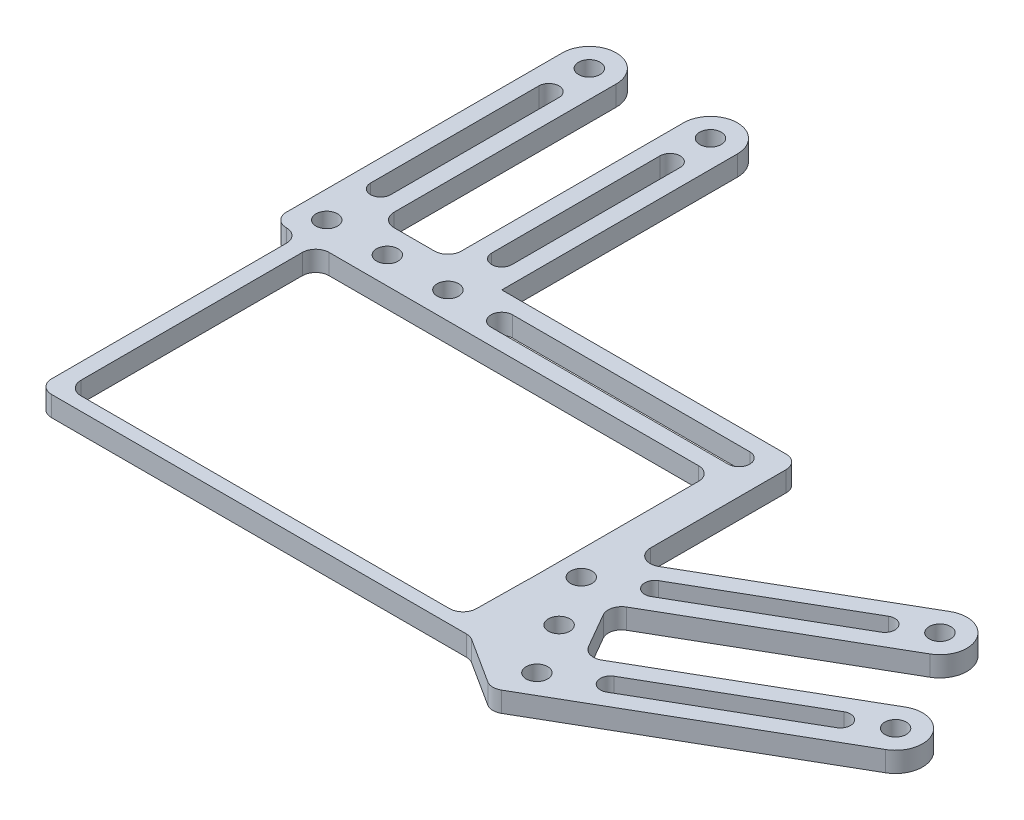
SolidWorks part; units mm, degrees
material "Thornel Mat VMA"
ref_plane "Front Plane" through (0, 0, 0) normal (0, 0, 1) x (1, 0, 0)
ref_plane "Top Plane" through (0, 0, 0) normal (0, 1, 0) x (1, 0, 0)
ref_plane "Right Plane" through (0, 0, 0) normal (1, 0, 0) x (0, 0, -1)
other "Configuration Table"
sketch "Sketch1" plane through (0, 0, 0) normal (0, 1, 0) x (1, 0, 0)
  line L0 (0, -4) -> (0, -42.8799)
  line L1 (0, -42.8799) -> (64.2212, -42.8799)
  line B0 (-4, -4) -> (61.235, -4)
  line B1 (61.235, -4) -> (61.235, -28.7731)
  line B2 (61.235, -28.7731) -> (72.3984, -48.1086)
  line B3 (72.3984, -48.1086) -> (79.3266, -44.1086)
  line B4 (64.8625, -27.0561) -> (73.8625, -42.6445) construction
  line B5 (79.3266, -44.1086) -> (66.235, -21.4334)
  line B6 (66.235, -21.4334) -> (66.235, 4)
  line B7 (66.235, 4) -> (-4, 4)
  line B8 (-4, 4) -> (-4, -4)
  line B9 (2.3607, -4) -> (2.3607, -40.8799)
  line B10 (2.3607, -40.8799) -> (61.0934, -40.8799)
  line B11 (61.0934, -40.8799) -> (72.3984, -48.1086)
  line B12 (61.235, -28.7731) -> (61.0934, -40.8799)
  line B13 (0, 0) -> (-4, 0) construction
  line B14 (73.8625, -42.6445) -> (75.8625, -46.1086) construction
  circle B15 centre (73.8625, -42.6445) radius 1.6
  circle B16 centre (69.3625, -34.8503) radius 1.6
  circle B17 centre (64.8625, -27.0561) radius 1.6
  circle B18 centre (0, 0) radius 1.6
  circle B19 centre (9, 0) radius 1.6
  circle B20 centre (18, 0) radius 1.6
  dimension "D1" = 2
sketch_block_instance "Block1-1"
sketch_block "Block1"
extrude "Boss-Extrude1" add sketch "Sketch1" along normal blind 3 contours B7 B8 B0 B1 B2 B3 B5 B6 B20 B19 B18 B17 B16 B15 | B11 B10 B9 B0 L0 L1 | B2 B12 B11 region at (1.1804, 0, 4.7507) region at (-2, 0, 3.0172) region at (64.909, 0, 39.2539)
fillet "Fillet1" radius 2 5 edges at (61.235, 1.5, 28.7731) (61.235, 1.5, 4) (2.3607, 1.5, 40.8799) (61.0934, 1.5, 40.8799) (2.3607, 1.5, 4)
fillet "Fillet2" radius 2 9 edges at (0, 1.5, 4) (-4, 1.5, 4) (-4, 1.5, -4) (66.235, 1.5, -4) (66.235, 1.5, 21.4334) (79.3266, 1.5, 44.1086) (72.3984, 1.5, 48.1086) (64.2212, 1.5, 42.8799) (0, 1.5, 42.8799)
sketch "Sketch2" plane through (0, 3, 0) normal (0, 1, 0) x (1, 0, 0)
  line L0 (26, 0) -> (61.235, 0) construction
  line L1 (26, 1.6) -> (61.235, 1.6)
  line L2 (26, -1.6) -> (61.235, -1.6)
  line L3 (61.235, -6) -> (61.235, -28.7614) construction
  arc A0 (26, 1.6) -> (26, -1.6) centre (26, 0) ccw
  arc A1 (61.235, -1.6) -> (61.235, 1.6) centre (61.235, 0) ccw
  circle A2 centre (18, 0) radius 1.6 construction
  point P3 (43.6175, 0)
  point P10 (0, 0)
  point P11 (0, 0)
  point P14 (26.0311, 0)
  dimension "D1" = 8
extrude "Cut-Extrude1" cut sketch "Sketch2" against normal blind 3
sketch "Sketch4" plane through (0, 3, 0) normal (0, 1, 0) x (1, 0, 0)
  circle A0 centre (64.8625, -27.0561) radius 1.6 construction
  circle A1 centre (73.8625, -42.6445) radius 1.6 construction
  circle A2 centre (73.8625, -42.6445) radius 1.6
  circle A3 centre (64.8625, -27.0561) radius 1.6
  circle A4 centre (0, 0) radius 1.6 construction
  circle A5 centre (0, 0) radius 1.6
  circle A6 centre (18, 0) radius 1.6 construction
  circle A7 centre (18, 0) radius 1.6
  circle B0 centre (69.3625, -34.8503) radius 1.6
  circle B1 centre (9, 0) radius 1.6
  line B2 (0, 0) -> (0, 39) construction
  line B3 (4, 0) -> (4, 39)
  line B4 (62.8625, -23.592) -> (96.6375, -4.092)
  arc B5 (100.6375, -11.0202) -> (96.6375, -4.092) centre (98.6375, -7.5561) ccw
  line B6 (66.8625, -30.5202) -> (100.6375, -11.0202)
  arc B7 (62.8625, -23.592) -> (66.8625, -30.5202) centre (64.8625, -27.0561) ccw
  line B8 (71.8625, -39.1804) -> (105.6375, -19.6804)
  arc B9 (109.6375, -26.6086) -> (105.6375, -19.6804) centre (107.6375, -23.1445) ccw
  line B10 (75.8625, -46.1086) -> (109.6375, -26.6086)
  arc B11 (71.8625, -39.1804) -> (75.8625, -46.1086) centre (73.8625, -42.6445) ccw
  line B12 (-4, 0) -> (-4, 39)
  arc B13 (4, 39) -> (-4, 39) centre (0, 39) ccw
  arc B14 (-4, 0) -> (4, 0) centre (0, 0) ccw
  line B15 (14, 0) -> (14, 39)
  arc B16 (22, 39) -> (14, 39) centre (18, 39) ccw
  line B17 (22, 0) -> (22, 39)
  arc B18 (14, 0) -> (22, 0) centre (18, 0) ccw
  line B19 (64.8625, -27.0561) -> (98.6375, -7.5561) construction
  line B20 (73.8625, -42.6445) -> (107.6375, -23.1445) construction
  line B21 (18, 0) -> (18, 39) construction
  arc M15 (77.5946, -45.1086) -> (78.3266, -42.3766) centre (76.5946, -43.3766) ccw
  line M16 (78.3266, -42.3766) -> (66.503, -21.8975)
  arc M17 (66.503, -21.8975) -> (66.235, -20.8975) centre (68.235, -20.8975) cw
  line M20 (64.235, 4) -> (-2, 4)
  arc M21 (-2, 4) -> (-4, 2) centre (-2, 2) ccw
sketch_block_instance "Block8-1"
sketch_block "Block8" parameters "D1"=4
extrude "Boss-Extrude2" add sketch "Sketch4" against normal blind 3 contours B3 B13 B12 M21 M20 | B17 B16 B15 M20 | B6 B5 B4 M17 M16 | B10 B9 B8 M16 M15 region at (18, 3, -23.0812) region at (-0.01, 3, -23.0265) region at (93.809, 3, 31.1399) region at (84.8517, 3, 15.5154)
sketch "Sketch5" plane through (0, 3, 0) normal (0, 1, 0) x (1, 0, 0)
  line L0 (61.235, -6) -> (61.235, -28.7614) construction
  line L1 (61.235, -23.3633) -> (55.5068, -23.3633)
  line L2 (61.235, -23.3633) -> (61.235, -31.1445)
  line L3 (61.235, -31.1445) -> (55.5068, -31.1445)
  line L4 (55.5068, -23.3633) -> (55.5068, -31.1445)
extrude "Cut-Extrude2" cut sketch "Sketch5" against normal blind 3
sketch "Sketch6" plane through (0, 3, 0) normal (0, 1, 0) x (1, 0, 0)
  circle A0 centre (0, 39) radius 1.6
  circle A1 centre (18, 39) radius 1.6
  circle A2 centre (98.6375, -7.5561) radius 1.6
  circle A3 centre (107.6375, -23.1445) radius 1.6
  dimension "D1" = 3.2
extrude "Cut-Extrude3" cut sketch "Sketch6" against normal blind 3
fillet "Fillet3" radius 2 5 edges at (14, 1.5, -4) (4, 1.5, -4) (75.3266, 1.5, 37.1804) (70.3266, 1.5, 28.5202) (66.3538, 1.5, 21.5763)
sketch "Sketch8" plane through (0, 3, 0) normal (0, 1, 0) x (1, 0, 0)
  line L0 (0, 33) -> (0, 8) construction
  line L1 (1.5, 33) -> (1.5, 8)
  line L2 (-1.5, 33) -> (-1.5, 8)
  line L3 (18, 33) -> (18, 8) construction
  line L4 (19.5, 33) -> (19.5, 8)
  line L5 (16.5, 33) -> (16.5, 8)
  line L6 (93.4413, -10.5561) -> (71.7907, -23.0561) construction
  line L7 (94.1913, -11.8551) -> (72.5407, -24.3551)
  line L8 (92.6913, -9.257) -> (71.0407, -21.757)
  line L9 (102.4413, -26.1445) -> (80.7907, -38.6445) construction
  line L10 (103.1913, -27.4436) -> (81.5407, -39.9436)
  line L11 (101.6913, -24.8455) -> (80.0407, -37.3455)
  line L12 (4, 6) -> (4, 39) construction
  line L13 (18, 39) -> (18, 33) construction
  line L14 (93.4413, -10.5561) -> (102.4413, -26.1445) construction
  line L15 (93.4413, -10.5561) -> (98.6375, -7.5561) construction
  line L16 (69.235, -19.9128) -> (96.6375, -4.092) construction
  line L17 (102.4413, -26.1445) -> (107.6375, -23.1445) construction
  arc A0 (1.5, 33) -> (-1.5, 33) centre (0, 33) ccw
  arc A1 (-1.5, 8) -> (1.5, 8) centre (0, 8) ccw
  arc A2 (19.5, 33) -> (16.5, 33) centre (18, 33) ccw
  arc A3 (16.5, 8) -> (19.5, 8) centre (18, 8) ccw
  arc A4 (94.1913, -11.8551) -> (92.6913, -9.257) centre (93.4413, -10.5561) ccw
  arc A5 (71.0407, -21.757) -> (72.5407, -24.3551) centre (71.7907, -23.0561) ccw
  arc A6 (103.1913, -27.4436) -> (101.6913, -24.8455) centre (102.4413, -26.1445) ccw
  arc A7 (80.0407, -37.3455) -> (81.5407, -39.9436) centre (80.7907, -38.6445) ccw
  point P3 (0, 20.5)
  point P8 (18, 20.5)
  point P15 (82.616, -16.8061)
  point P22 (91.616, -32.3945)
  dimension "D1" = 1.5
  dimension "D2" = 1.5
  dimension "D5" = 1.5
  dimension "D3" = 25
  dimension "D4" = 6
  dimension "D6" = 6
  dimension "D7" = 25
extrude "Cut-Extrude4" cut sketch "Sketch8" against normal blind 3
sketch "Sketch10" plane through (0, 3, 0) normal (0, 1, 0) x (1, 0, 0)
  circle B0 centre (0, 0) radius 1.6
  circle B1 centre (18, 39) radius 1.6
  circle B2 centre (0, 39) radius 1.6
  circle B3 centre (18, 0) radius 1.6
sketch_block_instance "Block2-1"
sketch_block "Block2"
